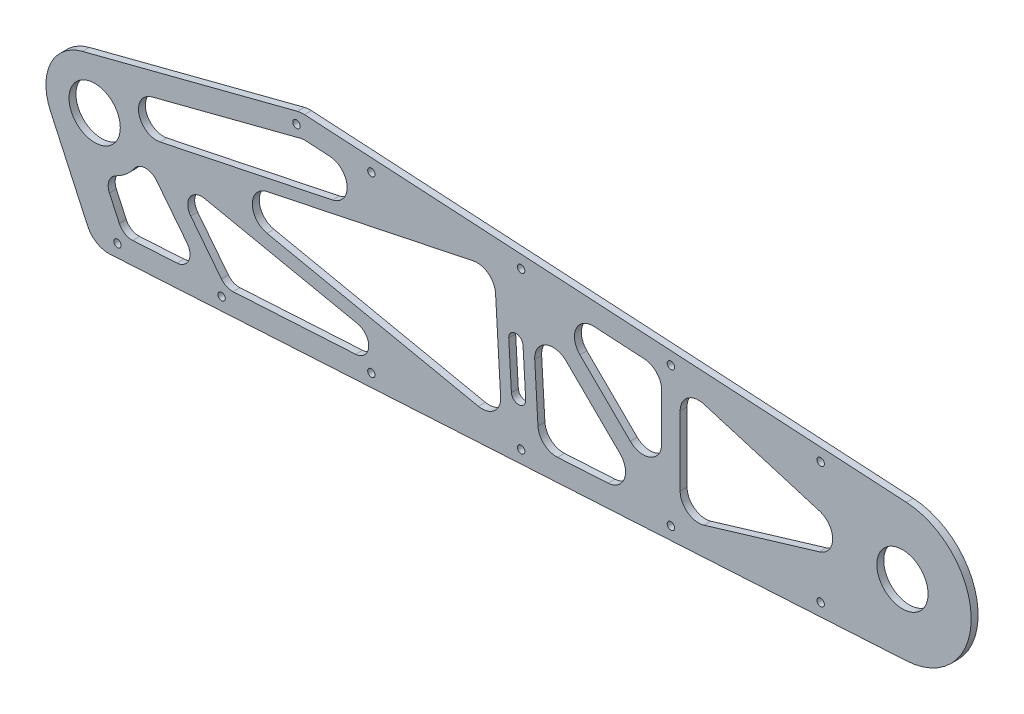
SolidWorks part; units mm, degrees
material "Thornel VCB-20 Carbon Cloth"
ref_plane "Front Plane" through (0, 0, 0) normal (0, 0, 1) x (1, 0, 0)
ref_plane "Top Plane" through (0, 0, 0) normal (0, 1, 0) x (1, 0, 0)
ref_plane "Right Plane" through (0, 0, 0) normal (1, 0, 0) x (0, 0, -1)
sketch "Sketch1" plane through (0, 0, 0) normal (0, 0, 1) x (1, 0, 0)
  line L0 (-175, 0) -> (175, 0) construction
  line L1 (-172.1122, 49.9165) -> (176.7203, 29.7354)
  line L2 (-172.1122, -49.9165) -> (176.7203, -29.7354)
  line L3 (139.566, 26.3757) -> (-120, 41.3925) construction
  line L4 (-55.1085, -37.6383) -> (9.783, -33.8841) construction
  line L5 (-125, 0) -> (-125, 62.9978) construction
  line L6 (-55.5713, 29.6383) -> (-120.4628, 33.3925) construction
  line L7 (-120.4628, 33.3925) -> (-120, 41.3925) construction
  line L8 (-55.5713, 29.6383) -> (-55.1085, 37.6383) construction
  line L9 (-88.0171, 31.5154) -> (-87.5543, 39.5154) construction
  line L10 (-120, -41.3925) -> (-165.1122, -44.0024) construction
  circle A0 centre (175, 0) radius 11.1125
  arc A1 (176.7203, 29.7354) -> (176.7203, -29.7354) centre (175, 0) cw
  circle A3 centre (-175, 0) radius 22.5 construction
  circle A7 centre (-175, 0) radius 11.1125
  circle A9 centre (-120, 41.3925) radius 1.6
  circle A10 centre (-55.1085, 37.6383) radius 1.6
  circle A11 centre (9.783, 33.8841) radius 1.6
  circle A12 centre (74.6745, 30.1299) radius 1.6
  circle A13 centre (139.566, 26.3757) radius 1.6
  circle A15 centre (139.566, -26.3757) radius 1.6
  circle A16 centre (74.6745, -30.1299) radius 1.6
  circle A17 centre (9.783, -33.8841) radius 1.6
  circle A18 centre (-55.1085, -37.6383) radius 1.6
  circle A19 centre (-120, -41.3925) radius 1.6
  arc A20 (-172.1122, 49.9165) -> (-172.1122, -49.9165) centre (-175, 0) ccw
  circle A21 centre (-87.5543, 39.5154) radius 1.6
  circle A22 centre (-165.1122, -44.0024) radius 1.6
  circle A23 centre (-165.1122, 44.0024) radius 1.6
  point P4 (0, 0)
  point P18 (-175, 22.5)
  point P21 (-197.5, 0)
  point P22 (-175, -22.5)
  point P23 (-152.5, 0)
  point P30 (-88.0171, 31.5154)
  dimension "D2" = 22.225
  dimension "D3" = 50
  dimension "D5" = 45
  dimension "D6" = 3.2
  dimension "D7" = 260
  dimension "D8" = 5
  dimension "D9" = 7
  dimension "D16" = 5
  dimension "D1" = 350
  dimension "D4" = 8
  dimension "D12" = 5.5
extrude "Boss-Extrude1" add sketch "Sketch1" along normal blind 3
sketch "Sketch4" plane through (0, 0, 3) normal (0, 0, 1) x (1, 0, 0)
  point P10 (-197.5, 0)
  point P13 (-175, 22.5)
  point P16 (-152.5, 0)
  point P19 (-175, -22.5)
hole_wizard "M3 Clearance Hole1" positions "Sketch4" profile "Sketch6" hole size "M3" standard "ANSI Metric" end condition up to next
sketch "Sketch6" plane through (-197.5, 0, 3) normal (1, 0, 0) x (0, -1, 0)
  line L0 (0, 0) -> (0, 3)
  line L1 (0, 3) -> (1.7, 3)
  line L2 (1.7, 3) -> (1.7, 0)
  line L5 (1.7, 0) -> (0, 0)
  line L11 (0, -6.35) -> (0, 107.95) construction
  dimension "Thru Hole Dia." = 3.4
  dimension "Thru Hole Depth" = 3
sketch "Sketch7" plane through (0, 0, 3) normal (0, 0, 1) x (1, 0, 0)
  line L0 (74.6745, 30.1299) -> (74.6745, -30.1299) construction
  line L1 (74.6745, -30.1299) -> (175, 0) construction
  line L2 (175, 0) -> (74.6745, 30.1299) construction
  line L3 (175, 0) -> (-152.5, 0) construction
  line L4 (175, -29.8349) -> (175, 29.8349) construction
  line L5 (88.9755, 22.7026) -> (139.0575, 7.6619)
  line L6 (139.0575, -7.6619) -> (88.9755, -22.7026)
  line L7 (78.6745, -15.0407) -> (78.6745, 15.0407)
  line L8 (9.783, -33.8841) -> (5.5294, 39.6394) construction
  line L9 (9.783, 33.8841) -> (74.6745, -30.1299) construction
  line L10 (9.783, 33.8841) -> (74.6745, 30.1299) construction
  line L11 (9.783, -33.8841) -> (74.6745, -30.1299) construction
  line L12 (-152.5, 0) -> (-55.1085, 37.6383) construction
  line L13 (-55.1085, 37.6383) -> (9.783, 33.8841) construction
  line L14 (9.783, 33.8841) -> (-152.5, 0) construction
  line L15 (70.6745, -1.436) -> (70.6745, 18.8041)
  line L16 (63.1365, 26.7907) -> (41.3408, 28.0517)
  line L17 (35.2605, 14.3698) -> (57.0563, -7.1312)
  line L18 (29.2743, 9.0376) -> (52.6422, -14.0143)
  line L19 (47.486, -27.6962) -> (25.5253, -28.9667)
  line L20 (17.0766, -21.4421) -> (15.6694, 2.8804)
  line L21 (176.7203, 29.7354) -> (-172.1122, 49.9165) construction
  line L22 (-172.1122, -49.9165) -> (176.7203, -29.7354) construction
  line L23 (0.8889, -18.6602) -> (-1.2973, 19.1278)
  line L24 (-10.9191, 26.4969) -> (-100.3161, 7.8311)
  line L25 (-100.3161, -7.8311) -> (-8.7329, -26.9534)
  line L35 (-197.5, 0) -> (-55.1085, 37.6383) construction
  line L52 (-55.1085, -37.6383) -> (-175, -22.5) construction
  line L53 (-15.2425, -47.7117) -> (-52.5586, -43) construction
  line L54 (-0.7058, -39.4678) -> (2.1851, -39.8329) construction
  line L55 (8.6627, -14.5198) -> (7.5076, 5.4468) construction
  line L56 (5.5679, -14.6989) -> (4.4127, 5.2678)
  line L57 (11.7575, -14.3408) -> (10.6024, 5.6258)
  line L58 (176.7203, 29.7354) -> (-172.1122, 49.9165) construction
  line L59 (-175, 22.5) -> (-165.1122, 44.0024) construction
  line L60 (-152.5, 0) -> (-120, 41.3925) construction
  line L61 (-133.3776, 17.8775) -> (-120.0806, 34.8127)
  line L62 (-115.0148, 37.0974) -> (-61.9156, 34.0254)
  line L63 (-61.0358, 22.1621) -> (-127.4321, 8.2988)
  line L64 (-168.5818, 26.883) -> (-164.3288, 36.1317)
  line L65 (-158.531, 39.6149) -> (-139.3382, 38.5046)
  line L66 (-134.9656, 28.8093) -> (-148.1724, 11.9888)
  line L67 (-179.2619, 22.8061) -> (-175.2558, 31.5179)
  line L68 (-197.5, 0) -> (-225, 0) construction
  line L69 (-208.0189, 4) -> (-200.2009, 4)
  line L70 (-208.0189, -4) -> (-200.2009, -4)
  line L71 (-179.2619, -22.8061) -> (-175.2558, -31.5179)
  line L72 (-168.5818, -26.883) -> (-164.3288, -36.1317)
  line L73 (-158.531, -39.6149) -> (-139.3382, -38.5046)
  line L74 (-134.9656, -28.8093) -> (-148.1724, -11.9888)
  line L75 (-115.0148, -37.0974) -> (-61.9156, -34.0254)
  line L76 (-133.3776, -17.8775) -> (-120.0806, -34.8127)
  line L77 (-61.0358, -22.1621) -> (-127.4321, -8.2988)
  arc A0 (139.0575, 7.6619) -> (139.0575, -7.6619) centre (136.7565, 0) cw
  arc A1 (88.9755, -22.7026) -> (78.6745, -15.0407) centre (86.6745, -15.0407) cw
  arc A2 (88.9755, 22.7026) -> (78.6745, 15.0407) centre (86.6745, 15.0407) ccw
  arc A3 (70.6745, 18.8041) -> (63.1365, 26.7907) centre (62.6745, 18.8041) ccw
  arc A4 (41.3408, 28.0517) -> (35.2605, 14.3698) centre (40.8787, 20.065) ccw
  arc A5 (70.6745, -1.436) -> (57.0563, -7.1312) centre (62.6745, -1.436) cw
  arc A6 (52.6422, -14.0143) -> (47.486, -27.6962) centre (47.024, -19.7095) cw
  arc A7 (25.5253, -28.9667) -> (17.0766, -21.4421) centre (25.0632, -20.98) cw
  arc A8 (29.2743, 9.0376) -> (15.6694, 2.8804) centre (23.6561, 3.3424) ccw
  arc A9 (0.8889, -18.6602) -> (-8.7329, -26.9534) centre (-7.0978, -19.1222) cw
  arc A10 (-1.2973, 19.1278) -> (-10.9191, 26.4969) centre (-9.2839, 18.6658) ccw
  arc A11 (-100.3161, 7.8311) -> (-100.3161, -7.8311) centre (-98.681, 0) ccw
  circle A30 centre (-175, 0) radius 11.1125 construction
  circle A31 centre (-175, 0) radius 11.1125 construction
  circle A32 centre (-175, 0) radius 22.5 construction
  circle A49 centre (9.783, -33.8841) radius 1.6 construction
  circle A50 centre (9.783, -33.8841) radius 1.6
  circle A52 centre (175, 0) radius 11.1125 construction
  circle A53 centre (175, 0) radius 11.1125 construction
  arc A56 (5.5679, -14.6989) -> (11.7575, -14.3408) centre (8.6627, -14.5198) ccw
  arc A57 (10.6024, 5.6258) -> (4.4127, 5.2678) centre (7.5076, 5.4468) ccw
  circle A58 centre (-165.1122, 44.0024) radius 1.6 construction
  circle A60 centre (-120, 41.3925) radius 1.6 construction
  arc A61 (-157.7842, 12.221) -> (-165.7573, 18.9818) centre (-175, 0) ccw
  arc A62 (-182.5636, 19.7111) -> (-194.624, 7.787) centre (-175, 0) ccw
  arc A63 (-181.6995, 39.942) -> (-213.7614, 11.7391) centre (-175, 0) ccw
  arc A64 (-172.1122, 49.9165) -> (-172.1122, -49.9165) centre (-175, 0) ccw construction
  arc A65 (-175.2558, 31.5179) -> (-181.6995, 39.942) centre (-180.707, 34.0247) ccw
  arc A66 (-213.7614, 11.7391) -> (-208.0189, 4) centre (-208.0189, 10) ccw
  arc A67 (-194.624, 7.787) -> (-200.2009, 4) centre (-200.2009, 10) cw
  arc A68 (-182.5636, 19.7111) -> (-179.2619, 22.8061) centre (-184.7131, 25.3129) ccw
  arc A69 (-61.9156, 34.0254) -> (-61.0358, 22.1621) centre (-62.2621, 28.0354) cw
  arc A70 (-120.0806, 34.8127) -> (-115.0148, 37.0974) centre (-115.3614, 31.1074) cw
  arc A71 (-133.3776, 17.8775) -> (-127.4321, 8.2988) centre (-128.6584, 14.1721) ccw
  arc A72 (-139.3382, 38.5046) -> (-134.9656, 28.8093) centre (-139.6847, 32.5146) cw
  arc A73 (-164.3288, 36.1317) -> (-158.531, 39.6149) centre (-158.8776, 33.625) cw
  arc A74 (-165.7573, 18.9818) -> (-168.5818, 26.883) centre (-163.1305, 24.3763) cw
  arc A75 (-157.7842, 12.221) -> (-148.1724, 11.9888) centre (-152.8916, 15.6941) ccw
  arc A76 (-213.7614, -11.7391) -> (-208.0189, -4) centre (-208.0189, -10) cw
  arc A77 (-194.624, -7.787) -> (-200.2009, -4) centre (-200.2009, -10) ccw
  arc A78 (-182.5636, -19.7111) -> (-194.624, -7.787) centre (-175, 0) cw
  arc A79 (-181.6995, -39.942) -> (-213.7614, -11.7391) centre (-175, 0) cw
  arc A80 (-182.5636, -19.7111) -> (-179.2619, -22.8061) centre (-184.7131, -25.3129) cw
  arc A81 (-175.2558, -31.5179) -> (-181.6995, -39.942) centre (-180.707, -34.0247) cw
  arc A82 (-164.3288, -36.1317) -> (-158.531, -39.6149) centre (-158.8776, -33.625) ccw
  arc A83 (-165.7573, -18.9818) -> (-168.5818, -26.883) centre (-163.1305, -24.3763) ccw
  arc A84 (-157.7842, -12.221) -> (-165.7573, -18.9818) centre (-175, 0) cw
  arc A85 (-157.7842, -12.221) -> (-148.1724, -11.9888) centre (-152.8916, -15.6941) cw
  arc A86 (-139.3382, -38.5046) -> (-134.9656, -28.8093) centre (-139.6847, -32.5146) ccw
  arc A87 (-61.9156, -34.0254) -> (-61.0358, -22.1621) centre (-62.2621, -28.0354) ccw
  arc A88 (-120.0806, -34.8127) -> (-115.0148, -37.0974) centre (-115.3614, -31.1074) ccw
  arc A89 (-133.3776, -17.8775) -> (-127.4321, -8.2988) centre (-128.6584, -14.1721) cw
  point P36 (164.5699, 0)
  point P59 (-137.8221, 0)
  point P102 (-15.2425, -47.7117)
  point P126 (8.0851, -4.5365)
  dimension "D8" = 8
  dimension "D11" = 10
  dimension "D12" = 5
  dimension "D20" = 3.1
  dimension "D10" = 4
  dimension "D17" = 6
  dimension "D1" = 3
  dimension "D3" = 8
  dimension "D4" = 8
  dimension "D5" = 8
  dimension "D6" = 16
  dimension "D7" = 6
  dimension "D9" = 8
  dimension "D13" = 8
  dimension "D14" = 5
  dimension "D15" = 8
  dimension "D16" = 24.8967
  dimension "D22" = 20
extrude "Cut-Extrude1" cut sketch "Sketch7" against normal blind 10 contours L57 A57 L56 A56 | L24 A11 L25 A9 L23 A10 | L18 A8 L20 A7 L19 A6 | A89 L76 A88 L75 A87 L77 | L20 A8 L18 A6 L19 A7 | L17 A5 L15 A3 L16 A4 | L7 A2 L5 A0 L6 A1 | L75 A87 L77 A89 L76 A88 | A82 L73 A86 L74 A85 A84 A83 L72 region at (32.1755, -11.823, 3) region at (-42.4165, -0.2065, 3) region at (8.0851, -4.5365, 3) region at (-98.5963, -24.3683, 3)
sketch "Sketch9" [suppressed] plane through (0, 0, 3) normal (0, 0, 1) x (1, 0, 0)
  line L2 (176.7203, 29.7354) -> (-172.1122, 49.9165) construction
  line L3 (-172.1122, -49.9165) -> (176.7203, -29.7354) construction
  line L4 (254.5375, 0) -> (208, 0) construction
  line L5 (200.557, 2) -> (203.931, 2)
  line L6 (200.557, -2) -> (203.931, -2)
  line L7 (162.9445, 26.3755) -> (155.7345, 26.7926)
  line L8 (162.9445, -26.3755) -> (155.7345, -26.7926)
  arc A1 (155.7345, -26.7926) -> (155.7345, 26.7926) centre (175, 0) ccw
  arc A2 (176.7203, -29.7354) -> (176.7203, 29.7354) centre (175, 0) ccw construction
  arc A3 (200.557, -2) -> (200.557, 2) centre (175, 0) ccw
  arc A4 (162.9445, 26.3755) -> (203.931, 2) centre (175, 0) cw
  arc A5 (203.931, -2) -> (162.9445, -26.3755) centre (175, 0) cw
  dimension "D1" = 33
  dimension "D2" = 4
  dimension "D3" = 4
extrude "Boss-Extrude2" [suppressed] add sketch "Sketch9" against normal up to surface (3 mm away) up to face at (56.1489, 13.0862, 0)
fillet "Fillet1" [suppressed] radius 1
fillet "Fillet2" [suppressed] radius 80
sketch "Sketch10" plane through (0, 0, 3) normal (0, 0, 1) x (1, 0, 0)
  line L0 (-165.1122, 44.0024) -> (-120, 41.3925) construction
  line L1 (-165.1122, 44.0024) -> (-210.2243, 46.6123) construction
  line L2 (-172.1122, 49.9165) -> (-210.905, 52.1608)
  line L3 (176.7203, 29.7354) -> (-172.1122, 49.9165) construction
  line L4 (-216.1854, 47.458) -> (-217.3977, 26.5035)
  line L5 (-172.1122, 49.9165) -> (-217.3977, 26.5035)
  circle A0 centre (-120, 41.3925) radius 1.6 construction
  circle A1 centre (-165.1122, 44.0024) radius 1.6 construction
  circle A2 centre (-210.2243, 46.6123) radius 1.6
  arc A3 (-172.1122, 49.9165) -> (-172.1122, -49.9165) centre (-175, 0) ccw construction
  arc A4 (-210.905, 52.1608) -> (-216.1854, 47.458) centre (-211.1938, 47.1692) ccw
  dimension "D2" = 5
  dimension "D1" = 6
extrude "Boss-Extrude3" [suppressed] add sketch "Sketch10" against normal up to surface (3 mm away) up to face at (56.1489, 13.0862, 0)
mirror "Mirror1" [suppressed] about plane through (0, 0, 0) normal (0, 1, 0)
sketch "Sketch13" plane through (0, 0, 3) normal (0, 0, 1) x (1, 0, 0)
  circle A1 centre (-120, 41.3925) radius 1.6 construction
  circle A2 centre (-165.1122, 44.0024) radius 1.6 construction
  circle A3 centre (-152.5, 0) radius 1.7 construction
  circle A4 centre (-175, 22.5) radius 1.7 construction
  circle A5 centre (-197.5, 0) radius 1.7 construction
  circle A6 centre (-175, -22.5) radius 1.7 construction
  circle A8 centre (-120, 41.3925) radius 1.6
  circle A9 centre (-165.1122, 44.0024) radius 1.6
  circle A10 centre (-152.5, 0) radius 1.7
  circle A11 centre (-175, 22.5) radius 1.7
  circle A12 centre (-197.5, 0) radius 1.7
  circle A13 centre (-175, -22.5) radius 1.7
extrude "Boss-Extrude4" add sketch "Sketch13" against normal up to surface (3 mm away) up to face at (56.1489, 13.0862, 0)
sketch "Sketch12" plane through (0, 0, 0) normal (0, 0, 1) x (1, 0, 0)
  line L0 (176.7203, 29.7354) -> (-172.1122, 49.9165) construction
  line L1 (-180.2861, 20.44) -> (-85.6491, 44.9144)
  line L2 (176.7203, 29.7354) -> (-172.1122, 49.9165) construction
  line L3 (-175.2456, -49.9994) -> (-194.1816, -8.8206)
  line L4 (-168.5818, -26.883) -> (-164.3288, -36.1317) construction
  line L5 (-172.1122, 49.9165) -> (-85.6491, 44.9144)
  line L6 (-150.183, 18.4125) -> (-85.9253, 35.0304)
  line L7 (-146.6452, 3.2656) -> (-71.9712, 18.8573)
  line L9 (-10.9191, 26.4969) -> (-100.3161, 7.8311) construction
  line L10 (-83.4602, 35.2718) -> (-73.1442, 34.675)
  line L11 (63.1365, 26.7907) -> (41.3408, 28.0517) construction
  line L12 (-192.0137, 12.5009) -> (-87.5543, 39.5154) construction
  arc A0 (-194.1816, -8.8206) -> (-180.2861, 20.44) centre (-175, 0) cw
  arc A1 (-71.9712, 18.8573) -> (-73.1442, 34.675) centre (-73.6063, 26.6884) ccw
  arc A2 (-85.9253, 35.0304) -> (-83.4602, 35.2718) centre (-83.9223, 27.2852) cw
  arc A3 (-172.1122, 49.9165) -> (-172.1122, -49.9165) centre (-175, 0) ccw construction
  circle A4 centre (-175, 0) radius 11.1125 construction
  arc A6 (-175.2456, -49.9994) -> (-172.1122, 49.9165) centre (-175, 0) cw
  arc A7 (-172.1122, 49.9165) -> (-172.1122, -49.9165) centre (-175, 0) ccw construction
  circle A13 centre (-87.5543, 39.5154) radius 1.6 construction
  arc A14 (-150.183, 18.4125) -> (-146.6452, 3.2656) centre (-148.2352, 10.8808) ccw
  arc A15 (-157.7842, -12.221) -> (-180.2861, 20.44) centre (-175, 0) ccw construction
  dimension "D1" = 10
  dimension "D5" = 8
  dimension "D3" = 9.5
  dimension "D4" = 5
extrude "Cut-Extrude2" cut sketch "Sketch12" against normal through all both and the other way through all
fillet "Fillet3" radius 10 2 edges at (-85.6491, 44.9144, 1.5) (-175.2456, -49.9994, 1.5)
